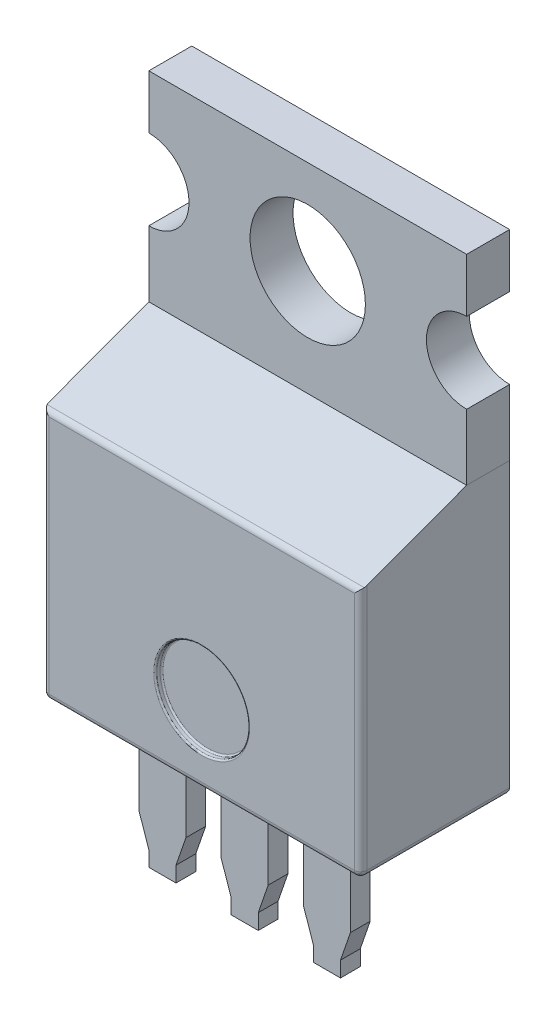
SolidWorks part; units mm, degrees
note: The reader was unsure of these and kept them because the rebuilt part matched: shared geometry of "Эскиз2<5>", "Эскиз3<5>", "Эскиз2<6>", "Эскиз3<6>", "Эскиз2<7>", "Эскиз5<2>".
ref_plane "Спереди" through (0, 0, 0) normal (0, 0, 1) x (1, 0, 0)
ref_plane "Сверху" through (0, 0, 0) normal (0, 1, 0) x (1, 0, 0)
ref_plane "Справа" through (0, 0, 0) normal (1, 0, 0) x (0, 0, -1)
sketch "Эскиз1" plane through (0, 0, 0) normal (0, 1, 0) x (1, 0, 0)
  line L0 (2.22, 0.32) -> (3.1, 0.32)
  line L1 (-0.44, 0.32) -> (0.44, 0.32)
  line L2 (-0.44, 0.32) -> (-0.44, -0.32)
  line L3 (-0.44, -0.32) -> (0.44, -0.32)
  line L4 (0.44, 0.32) -> (0.44, -0.32)
  line L5 (-0.44, 0.32) -> (0.44, -0.32) construction
  line L6 (-0.44, -0.32) -> (0.44, 0.32) construction
  line L7 (2.22, 0.32) -> (2.22, -0.32)
  line L8 (2.22, -0.32) -> (3.1, -0.32)
  line L9 (3.1, 0.32) -> (3.1, -0.32)
  line L10 (-3.1, 0.32) -> (-2.22, 0.32)
  line L11 (-3.1, 0.32) -> (-3.1, -0.32)
  line L12 (-3.1, -0.32) -> (-2.22, -0.32)
  line L13 (-2.22, 0.32) -> (-2.22, -0.32)
  point P0 (0, 0)
  dimension "D1" = 2
  dimension "D2" = 2
extrude "Бобышка-Вытянуть1" add sketch "Эскиз1" against normal blind 0.5
ref_plane "Плоскость1" through (0, 0.93, 0) normal (0, 1, 0) x (1, 0, 0)
sketch "Эскиз2" plane through (0, 0.93, 0) normal (0, 1, 0) x (1, 0, 0)
  line L1 (-0.76, 0.32) -> (0.76, 0.32)
  line L2 (-0.76, 0.32) -> (-0.76, -0.32)
  line L3 (-0.76, -0.32) -> (0.76, -0.32)
  line L4 (0.76, 0.32) -> (0.76, -0.32)
  line L5 (-0.76, 0.32) -> (0.76, -0.32) construction
  line L6 (-0.76, -0.32) -> (0.76, 0.32) construction
  line L7 (1.9, 0.32) -> (1.9, -0.32)
  line L8 (1.9, 0.32) -> (3.42, 0.32)
  line L9 (1.9, -0.32) -> (3.42, -0.32)
  line L10 (3.42, 0.32) -> (3.42, -0.32)
  line L11 (-3.42, 0.32) -> (-3.42, -0.32)
  line L12 (-3.42, 0.32) -> (-1.9, 0.32)
  line L13 (-3.42, -0.32) -> (-1.9, -0.32)
  line L14 (-1.9, 0.32) -> (-1.9, -0.32)
  point P0 (0, 0)
  dimension "D1" = 2
  dimension "D2" = 2
sketch "Эскиз3" plane through (0, 0, 0) normal (0, 1, 0) x (1, 0, 0)
  line L1 (-3.1, 0.32) -> (-2.22, 0.32)
  line L2 (-3.1, 0.32) -> (-3.1, -0.32)
  line L3 (-3.1, -0.32) -> (-2.22, -0.32)
  line L4 (-2.22, 0.32) -> (-2.22, -0.32)
  line L5 (-0.44, 0.32) -> (0.44, 0.32)
  line L6 (-0.44, 0.32) -> (-0.44, -0.32)
  line L7 (-0.44, -0.32) -> (0.44, -0.32)
  line L8 (0.44, 0.32) -> (0.44, -0.32)
  line L9 (2.22, 0.32) -> (3.1, 0.32)
  line L10 (2.22, 0.32) -> (2.22, -0.32)
  line L11 (2.22, -0.32) -> (3.1, -0.32)
  line L12 (3.1, 0.32) -> (3.1, -0.32)
loft "По сечениям1" add section "Эскиз3" section "Эскиз2"
loft "По сечениям2" add section "Эскиз2<5>" section "Эскиз3<5>"
sketch "Эскиз2<5>" plane through (0, 0.93, 0) normal (0, 1, 0) x (1, 0, 0) same geometry as "Эскиз2"
sketch "Эскиз3<5>" plane through (0, 0, 0) normal (0, 1, 0) x (1, 0, 0) same geometry as "Эскиз3"
loft "По сечениям3" add section "Эскиз2<6>" section "Эскиз3<6>"
sketch "Эскиз2<6>" plane through (0, 0.93, 0) normal (0, 1, 0) x (1, 0, 0) same geometry as "Эскиз2"
sketch "Эскиз3<6>" plane through (0, 0, 0) normal (0, 1, 0) x (1, 0, 0) same geometry as "Эскиз3"
extrude "Бобышка-Вытянуть2" add sketch "Эскиз2<7>" along normal blind 3
sketch "Эскиз2<7>" plane through (0, 0.93, 0) normal (0, 1, 0) x (1, 0, 0) same geometry as "Эскиз2"
sketch "Эскиз4" plane through (0, 3.93, 0) normal (0, 1, 0) x (1, 0, 0)
  line L1 (-5.14, 3.11) -> (5.14, 3.11)
  line L2 (-5.14, 3.11) -> (-5.14, -1.71)
  line L3 (-5.14, -1.71) -> (5.14, -1.71)
  line L4 (5.14, 3.11) -> (5.14, -1.71)
  line L5 (-5.14, 3.11) -> (5.14, -1.71) construction
  line L6 (-5.14, -1.71) -> (5.14, 3.11) construction
  point P0 (0, 0.7)
  point P5 (0, 0)
  point P6 (0, 0)
  point P7 (0, 0)
  point P8 (0, 0)
  point P9 (0, 0)
  point P10 (0, 0)
  point P11 (0, 0)
  point P12 (0, 0)
  point P13 (0, 0)
  point P14 (0, 0)
  point P15 (0, 0)
  point P16 (0, 0)
extrude "Бобышка-Вытянуть3" add sketch "Эскиз4" along normal blind 8.1
ref_plane "Плоскость2" through (0, 13.3, 0) normal (0, 1, 0) x (1, 0, 0)
sketch "Эскиз5" plane through (0, 13.3, 0) normal (0, 1, 0) x (1, 0, 0)
  line L0 (5.14, -1.71) -> (5.14, 3.11) construction
  line L1 (-5.14, 3.11) -> (5.14, 3.11)
  line L2 (-5.14, 3.11) -> (-5.14, 1.72)
  line L3 (-5.14, 1.72) -> (5.14, 1.72)
  line L4 (5.14, 3.11) -> (5.14, 1.72)
loft "По сечениям4" add profiles "Эскиз5" section "Эскиз5" section face at (0, 12.03, -0.7)
extrude "Бобышка-Вытянуть4" add sketch "Эскиз5<2>" along normal blind 6.47 separate body
sketch "Эскиз5<2>" plane through (0, 13.3, 0) normal (0, 1, 0) x (1, 0, 0) same geometry as "Эскиз5"
sketch "Эскиз8" plane through (0, 0, -1.72) normal (0, 0, 1) x (1, 0, 0)
  line L0 (-5.14, 19.77) -> (5.14, 19.77)
  line L1 (0, 19.77) -> (0, 16.73)
  line L2 (0, -50) -> (0, 50) construction
  circle A0 centre (0, 16.73) radius 1.865
extrude "Вырез-Вытянуть1" cut sketch "Эскиз8" against normal blind 1.39 contours A0
sketch "Эскиз9" plane through (0, 0, 1.71) normal (0, 0, 1) x (1, 0, 0)
  line L0 (-5.14, 3.93) -> (5.14, 3.93)
  line L1 (0, 3.93) -> (0, 6.43)
  circle A0 centre (0, 6.43) radius 1.5
extrude "Вырез-Вытянуть2" cut sketch "Эскиз9" against normal blind 0.2 contours A0
fillet "Скругление2" radius 0.05 2 edges at (1.5, 6.43, 1.71) (1.5, 6.43, 1.51)
sketch "Эскиз10" plane through (0, 0, -1.72) normal (0, 0, 1) x (1, 0, 0)
  line L1 (5.14, 19.77) -> (5.14, 16.73)
  line L2 (5.14, 19.77) -> (5.14, 13.3) construction
  line L3 (-5.14, 19.77) -> (-5.14, 16.73)
  line L4 (-5.14, 19.77) -> (-5.14, 13.3) construction
  circle A0 centre (5.14, 16.73) radius 1.3
  circle A1 centre (-5.14, 16.73) radius 1.3
extrude "Вырез-Вытянуть3" cut sketch "Эскиз10" against normal blind 1.39 contours A0 | A1
fillet "Скругление4" radius 0.2 7 edges at (-5.14, 3.93, -0.7) (0, 3.93, -3.11) (5.14, 3.93, -0.7) (0, 3.93, 1.71)
